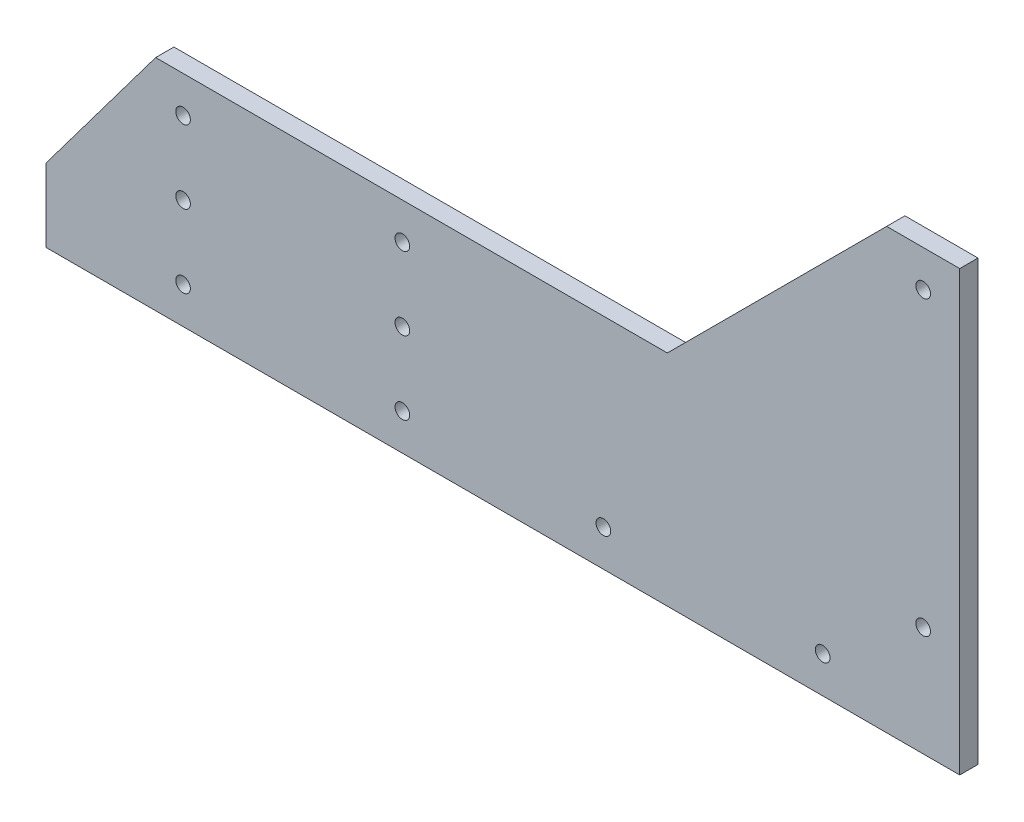
SolidWorks part; units mm, degrees
ref_plane "Front" through (0, 0, 0) normal (0, 0, 1) x (1, 0, 0)
ref_plane "Top" through (0, 0, 0) normal (0, 1, 0) x (1, 0, 0)
ref_plane "Right" through (0, 0, 0) normal (1, 0, 0) x (0, 0, -1)
sketch "Esquisse1" plane through (0, 0, 0) normal (0, 0, 1) x (1, 0, 0)
  line L1 (0, 0) -> (250, 0)
  line L2 (0, 0) -> (0, 60)
  line L3 (0, 60) -> (250, 60)
  line L4 (250, 0) -> (250, 60)
  dimension "D1" = 250
  dimension "D2" = 60
extrude "Boss.-Extru.1" add sketch "Esquisse1" along normal blind 5
sketch "Esquisse4" plane through (0, 0, 5) normal (0, 0, 1) x (1, 0, 0)
  line L0 (250, 60) -> (250, 120)
  line L1 (250, 120) -> (230, 120)
  line L2 (230, 120) -> (170, 60)
  line L3 (250, 60) -> (0, 60) construction
  line L4 (170, 60) -> (250, 60)
  dimension "D1" = 45
  dimension "D2" = 20
  dimension "D3" = 60
extrude "Boss.-Extru.2" add sketch "Esquisse4" against normal up to vertex (5 mm away) up to point (250, 60, 0)
sketch "Esquisse2" plane through (0, 0, 5) normal (0, 0, 1) x (1, 0, 0)
  line L0 (125, 0) -> (125, 60) construction
  line L1 (0, 0) -> (250, 0) construction
  line L2 (170, 60) -> (0, 60) construction
  line L3 (0, 10) -> (250, 10) construction
  line L4 (0, 60) -> (0, 0) construction
  line L5 (250, 0) -> (250, 120) construction
  line L6 (240, 60) -> (240, 110) construction
  line L7 (240, 110) -> (240, 30) construction
  line L8 (37.5, 10) -> (37.5, 60) construction
  line L9 (97.5, 10) -> (97.5, 60) construction
  line L10 (37.5, 35) -> (97.5, 35) construction
  line L11 (67.5, 35) -> (67.5, 60) construction
  line L12 (170, 60) -> (0, 60) construction
  circle A0 centre (37.5, 10) radius 2
  circle A1 centre (97.5, 10) radius 2
  circle A2 centre (152.5, 10) radius 2
  circle A3 centre (212.5, 10) radius 2
  circle A4 centre (240, 110) radius 2
  circle A5 centre (240, 30) radius 2
  circle A6 centre (37.5, 30) radius 2
  circle A7 centre (37.5, 50) radius 2
  circle A8 centre (97.5, 50) radius 2
  circle A9 centre (97.5, 30) radius 2
  point P39 (125, 0)
  point P40 (125, 60)
  point P43 (240, 93.8521)
  dimension "D1" = 60
  dimension "D2" = 55
  dimension "D3" = 4
  dimension "D6" = 80
  dimension "D7" = 30
  dimension "D8" = 10
  dimension "D9" = 30
  dimension "D4" = 10
  dimension "D5" = 10
extrude "Enlèv. mat.-Extru.1" cut sketch "Esquisse2" against normal up to vertex (5 mm away) up to point (250, 120, 0)
sketch "Esquisse3" plane through (0, 0, 5) normal (0, 0, 1) x (1, 0, 0)
  line L0 (0, 20) -> (30, 60)
  line L1 (0, 60) -> (0, 0) construction
  line L2 (170, 60) -> (0, 60) construction
  line L3 (30, 60) -> (0, 60)
  line L4 (0, 60) -> (0, 20)
  dimension "D1" = 20
  dimension "D2" = 30
extrude "Enlèv. mat.-Extru.2" cut sketch "Esquisse3" against normal through all both and the other way through all
